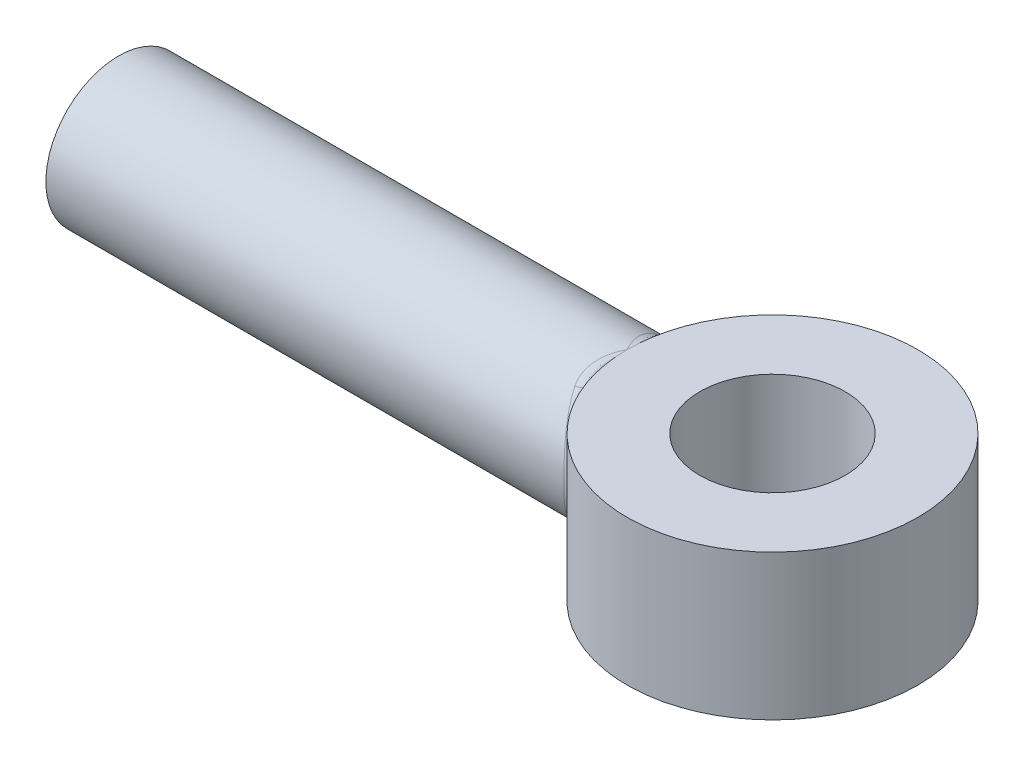
SolidWorks part; units mm, degrees
ref_plane "Front Plane" through (0, 0, 0) normal (0, 0, 1) x (1, 0, 0)
ref_plane "Top Plane" through (0, 0, 0) normal (0, 1, 0) x (1, 0, 0)
ref_plane "Right Plane" through (0, 0, 0) normal (1, 0, 0) x (0, 0, -1)
sketch "Sketch1" plane through (0, 0, 0) normal (0, 1, 0) x (1, 0, 0)
  circle A0 centre (0, 0) radius 2
  circle A1 centre (0, 0) radius 1
  dimension "D1" = 2
  dimension "D2" = 4
extrude "Boss-Extrude1" add sketch "Sketch1" along normal mid plane 2
sketch "Sketch2" plane through (0, 0, 0) normal (1, 0, 0) x (0, 0, -1)
  circle A0 centre (0, 0) radius 1
  dimension "D1" = 2
extrude "Boss-Extrude2" add sketch "Sketch2" along normal up to surface (7.2679 mm away) from offset 9 up to face at (0, 1, 2) offset against normal yes
fillet "Fillet1" radius 0.25 2 edges at (-1.7353, 0.1068, -0.9943) (-1.7353, -0.1068, -0.9943)
